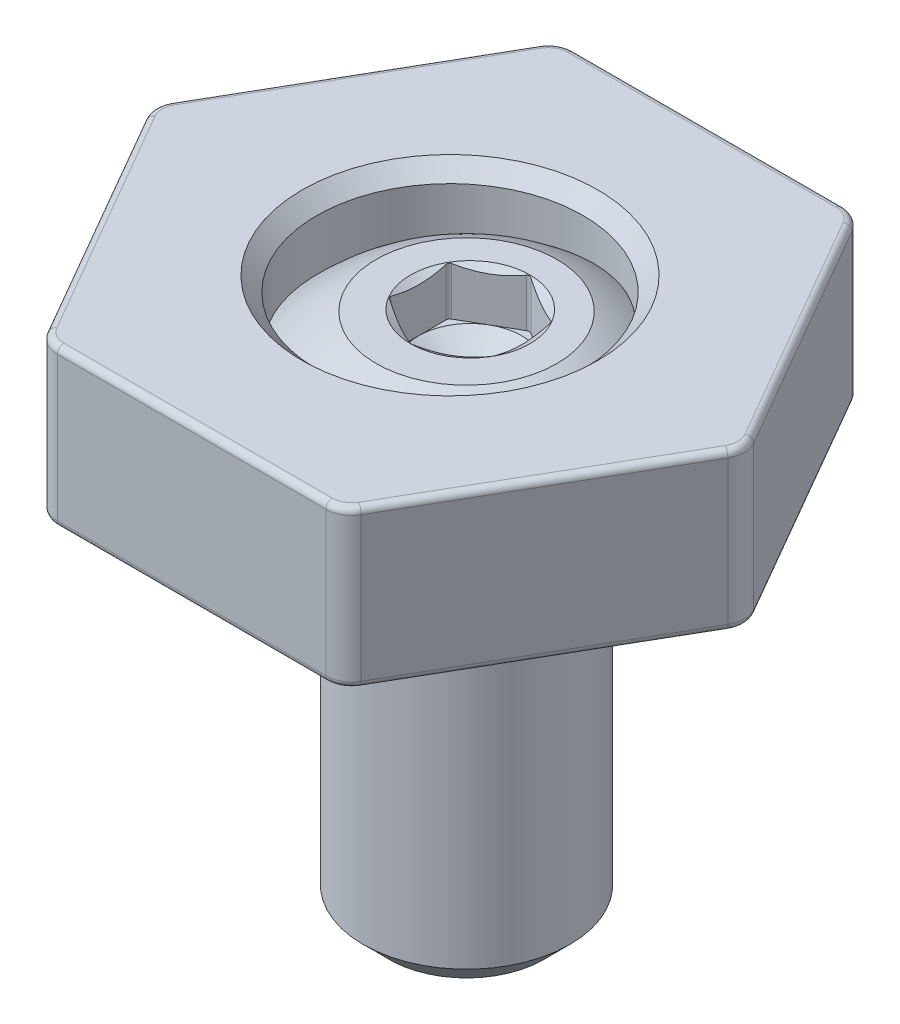
SolidWorks part; units mm, degrees
ref_plane "Front Plane" through (0, 0, 0) normal (0, 0, 1) x (1, 0, 0)
ref_plane "Top Plane" through (0, 0, 0) normal (0, 1, 0) x (1, 0, 0)
ref_plane "Right Plane" through (0, 0, 0) normal (1, 0, 0) x (0, 0, -1)
sketch "Sketch1" plane through (0, 0, 0) normal (0, 0, 1) x (1, 0, 0)
  line L0 (0, -8.382) -> (0, 8.382) construction
  line L1 (-4.0894, 8.382) -> (-7.9375, 8.382) construction
  line L2 (-7.9375, 8.382) -> (-7.9375, 3.556) construction
  line L9 (-4.0894, 8.382) -> (-4.0894, 4.318) construction
  line L10 (-3.8735, 3.556) -> (-7.9375, 3.556) construction
  line L11 (-4.0894, 4.318) -> (-3.8735, 4.318) construction
  line L12 (-3.8735, 4.318) -> (-3.8735, 3.556) construction
  line L13 (0.508, -8.382) -> (0.508, 8.382) construction
  line L14 (0.508, -8.382) -> (3.683, -8.382) construction
  line L15 (3.683, -8.382) -> (3.683, 4.318) construction
  line L16 (3.683, -8.382) -> (4.953, -8.382) construction
  line L17 (3.683, 4.318) -> (4.0259, 4.318) construction
  line L18 (4.0259, 4.318) -> (4.0259, 7.6708) construction
  arc A0 (4.0259, 7.2515) -> (3.283, 7.6708) centre (0.508, 1.8857) ccw construction
  point P3 (0, 0)
  point P26 (0.508, 6.1722)
  dimension "Screw Head Radius" = 6.4162
  dimension "Head C'Bore" = 8.1788
  dimension "Head Height" = 4.826
  dimension "Head ID" = 7.747
  dimension "Thread Length" = 11.938
  dimension "Maximum Head Movement" = 1.016
  dimension "Thread Size" = 6.35
  dimension "Pitch" = 1.27
  dimension "Shank Length" = 12.7
  dimension "Screw Head Diameter" = 8.0518
  dimension "Screw Head Height" = 3.3528
  dimension "Head Radius Center Offset" = 10.2677
  dimension "Drive Depth" = 2.2098
  dimension "Head Width" = 15.875
sketch "Sketch2" plane through (0, 0, 0) normal (0, 1, 0) x (1, 0, 0)
  line L0 (0.508, -1.7188) -> (0.508, 1.9474) construction
  line L1 (-1.0795, 1.0308) -> (-1.0795, -0.8022) construction
  line L2 (-1.0795, -0.8022) -> (0.508, -1.7188) construction
  line L3 (0.508, -1.7188) -> (2.0955, -0.8022) construction
  line L4 (2.0955, -0.8022) -> (2.0955, 1.0308) construction
  line L5 (2.0955, 1.0308) -> (0.508, 1.9474) construction
  line L6 (0.508, 1.9474) -> (-1.0795, 1.0308) construction
  line L7 (-3.8735, 0) -> (-7.9375, 0) construction
  line L8 (9.1654, 0) -> (4.5827, 7.9375)
  line L9 (4.5827, 7.9375) -> (-4.5827, 7.9375)
  line L10 (-4.5827, 7.9375) -> (-9.1654, 0)
  line L11 (-9.1654, 0) -> (-4.5827, -7.9375)
  line L12 (-4.5827, -7.9375) -> (4.5827, -7.9375)
  line L13 (4.5827, -7.9375) -> (9.1654, 0)
  circle A0 centre (0.508, 0.1143) radius 1.5875 construction
  circle A1 centre (0, 0) radius 7.9375 construction
  point P1 (0, 0)
  point P12 (1.016, 0)
  point P26 (-7.9375, 0)
  point P29 (0.508, 0)
  dimension "Drive Size" = 3.175
  dimension "Drill Location" = 7.8232
sketch "Sketch3" plane through (0, 0, 0) normal (0, 0, 1) x (1, 0, 0)
  line L0 (-3.8735, 3.556) -> (-7.9375, 3.556) construction
  line L1 (-4.543, 8.382) -> (-4.0894, 7.9284)
  line L8 (-4.0894, 8.382) -> (-7.9375, 8.382) construction
  line L9 (-4.0894, 8.382) -> (-4.0894, 4.318) construction
  line L10 (-4.0894, 4.318) -> (-3.8735, 4.318) construction
  line L11 (-3.8735, 4.318) -> (-3.8735, 3.556) construction
  line L12 (-3.8735, 3.556) -> (-7.9375, 3.556)
  line L20 (-4.543, 8.382) -> (-7.9375, 8.382)
  line L21 (-4.0894, 7.9284) -> (-4.0894, 4.318)
  line L22 (-4.0894, 4.318) -> (-3.8735, 4.318)
  line L23 (-3.8735, 4.318) -> (-3.8735, 3.556)
  line L24 (0, -8.382) -> (0, 8.382) construction
  line L25 (0, -8.382) -> (0, 8.382) construction
  line L26 (-7.9375, 8.382) -> (-7.9375, 3.556)
  dimension "D1" = 45
  dimension "D2" = 0.4536
revolve "Revolve1" add sketch "Sketch3" angle 360 about L25
sketch "Sketch4" plane through (0, 8.382, 0) normal (0, 1, 0) x (1, 0, 0)
  line L1 (4.1244, 7.9375) -> (-4.1244, 7.9375)
  line L2 (-4.8119, 7.5406) -> (-8.9363, 0.3969)
  line L3 (-8.9363, -0.3969) -> (-4.8119, -7.5406)
  line L4 (-4.1244, -7.9375) -> (4.1244, -7.9375)
  line L5 (4.8119, -7.5406) -> (8.9363, -0.3969)
  line L6 (8.9363, 0.3969) -> (4.8119, 7.5406)
  circle A0 centre (0, 0) radius 7.9375 construction
  circle A1 centre (0, 0) radius 7.9375 construction
  arc A2 (4.1244, 7.9375) -> (4.8119, 7.5406) centre (4.1244, 7.1438) cw
  arc A3 (-4.1244, 7.9375) -> (-4.8119, 7.5406) centre (-4.1244, 7.1437) ccw
  arc A4 (-8.9363, 0.3969) -> (-8.9363, -0.3969) centre (-8.2489, 0) ccw
  arc A5 (-4.8119, -7.5406) -> (-4.1244, -7.9375) centre (-4.1244, -7.1438) ccw
  arc A6 (4.1244, -7.9375) -> (4.8119, -7.5406) centre (4.1244, -7.1438) ccw
  arc A7 (8.9363, -0.3969) -> (8.9363, 0.3969) centre (8.2489, 0) ccw
  circle A9 centre (0, 0) radius 4.543
  circle A10 centre (0, 0) radius 4.543 construction
  dimension "D1" = 0.7937
extrude "Boss-Extrude1" add sketch "Sketch4" against normal up to surface (4.826 mm away) up to face at (3.8735, 3.556, 0)
fillet "Fillet1" radius 0.1984 24 edges at (-4.5213, 8.382, -7.8312) (0, 8.382, -7.9375) (4.5213, 8.382, -7.8312) (6.8741, 8.382, -3.9688) (9.0426, 8.382, 0) (6.8741, 8.382, 3.9688) (4.5213, 8.382, 7.8312) (0, 8.382, 7.9375) (-4.5213, 8.382, 7.8312) (-6.8741, 8.382, 3.9688) (-9.0426, 8.382, 0) (-9.0426, 3.556, 0) (-6.8741, 3.556, 3.9688) (-4.5213, 3.556, 7.8312) (0, 3.556, 7.9375) (4.5213, 3.556, 7.8312) (6.8741, 3.556, 3.9688) (9.0426, 3.556, 0) (6.8741, 3.556, -3.9688) (4.5213, 3.556, -7.8312) (0, 3.556, -7.9375) (-4.5213, 3.556, -7.8312) (-6.8741, 8.382, -3.9688) (-6.8741, 3.556, -3.9688)
sketch "Sketch5" plane through (0, 0, 0) normal (0, 0, 1) x (1, 0, 0)
  line L0 (0, -8.382) -> (0, 8.382) construction
  line L1 (0, -8.382) -> (0, 8.382) construction
  line L2 (0, 4.318) -> (4.0259, 4.318)
  line L3 (4.0259, 4.318) -> (4.0259, 7.6708)
  line L4 (4.0259, 7.6708) -> (0, 7.6708)
  line L5 (0, 7.6708) -> (0, 4.318) construction
  line L6 (0, 4.318) -> (0, 7.6708)
revolve "Revolve2" add sketch "Sketch5" angle 360 about L6
sketch "Sketch6" plane through (0, 0, 0) normal (0, 0, 1) x (1, 0, 0)
  line L0 (0.508, -8.382) -> (0.508, 4.318) construction
  line L1 (0.508, -8.382) -> (0.508, 8.382) construction
  line L2 (-4.0259, 4.318) -> (4.0259, 4.318) construction
  line L3 (0.508, 4.318) -> (3.683, 4.318)
  line L4 (3.683, 4.318) -> (3.683, -7.5882)
  line L5 (3.683, -8.382) -> (3.683, 4.318) construction
  line L6 (3.683, -7.5882) -> (2.8893, -8.382)
  line L7 (0.508, -8.382) -> (3.683, -8.382) construction
  line L8 (2.8893, -8.382) -> (0.508, -8.382)
  line L9 (0.508, -8.382) -> (0.508, 4.318)
  point P12 (3.683, -2.667)
  dimension "D1" = 45
  dimension "D2" = 0.7937
  dimension "D3" = 5.715
revolve "Revolve3" add sketch "Sketch6" angle 360 about L0
sketch "Sketch7" plane through (0, 0, 0) normal (0, 0, 1) x (1, 0, 0)
  line L0 (0.508, -8.382) -> (0.508, 8.382) construction
  line L5 (6.703, 13.1279) -> (6.703, 3.556)
  line L6 (0.508, -8.382) -> (0.508, 8.3019) construction
  line L7 (0.508, 8.3019) -> (0.508, 13.1279)
  line L8 (0.508, 13.1279) -> (6.703, 13.1279)
  line L9 (-6.703, 8.382) -> (6.703, 8.382) construction
  line L10 (-7.9375, 8.382) -> (-7.9375, 3.556) construction
  line L11 (-3.8735, 3.556) -> (-7.9375, 3.556) construction
  arc A0 (6.703, 3.556) -> (0.508, 8.3019) centre (0.508, 1.8857) ccw
  arc A1 (4.0259, 7.2515) -> (3.283, 7.6708) centre (0.508, 1.8857) ccw construction
  point P14 (0, 8.382)
revolve "Cut-Revolve1" cut sketch "Sketch7" angle 360 about L0
sketch "Sketch8" plane through (0, 7.6708, 0) normal (0, 1, 0) x (1, 0, 0)
  line L0 (-1.0795, -0.8022) -> (0.508, -1.7188) construction
  line L1 (0.508, -1.7188) -> (2.0955, -0.8022) construction
  line L2 (2.0955, -0.8022) -> (2.0955, 1.0308) construction
  line L3 (2.0955, 1.0308) -> (0.508, 1.9474) construction
  line L4 (0.508, 1.9474) -> (-1.0795, 1.0308) construction
  line L5 (-1.0795, 1.0308) -> (-1.0795, -0.8022) construction
  line L6 (-1.016, -0.8389) -> (0.4445, -1.6821)
  line L7 (0.5715, -1.6821) -> (2.032, -0.8389)
  line L8 (2.0955, -0.7289) -> (2.0955, 0.9575)
  line L9 (2.032, 1.0675) -> (0.5715, 1.9107)
  line L10 (0.4445, 1.9107) -> (-1.016, 1.0675)
  line L11 (-1.0795, 0.9575) -> (-1.0795, -0.7289)
  arc A0 (0.5715, 1.9107) -> (0.4445, 1.9107) centre (0.508, 1.8007) ccw
  arc A1 (2.0955, 0.9575) -> (2.032, 1.0675) centre (1.9685, 0.9575) ccw
  arc A2 (2.032, -0.8389) -> (2.0955, -0.7289) centre (1.9685, -0.7289) ccw
  arc A3 (-1.016, 1.0675) -> (-1.0795, 0.9575) centre (-0.9525, 0.9575) ccw
  arc A4 (0.4445, -1.6821) -> (0.5715, -1.6821) centre (0.508, -1.5721) ccw
  arc A5 (-1.016, -0.8389) -> (-1.0795, -0.7289) centre (-0.9525, -0.7289) cw
  dimension "D1" = 0.127
extrude "Cut-Extrude1" cut sketch "Sketch8" against normal up to vertex (1.4986 mm away) up to point (0.508, 6.1722, 0)
sketch "Sketch9" plane through (0, 6.1722, 0) normal (0, 1, 0) x (1, 0, 0)
  circle A0 centre (0.508, 0.1143) radius 1.5875 construction
  circle A1 centre (0.508, 0.1143) radius 1.5875
extrude "Cut-Extrude2" cut sketch "Sketch9" against normal through all draft 59
sketch "Sketch10" plane through (0, 7.6708, 0) normal (0, 1, 0) x (1, 0, 0)
  circle A0 centre (0.508, 0.1143) radius 1.8331
extrude "Cut-Extrude3" cut sketch "Sketch10" against normal through all draft 60
sketch "Sketch11" [suppressed] plane through (0, -8.382, 0) normal (0, -1, 0) x (1, 0, 0)
  circle A0 centre (0.508, 0) radius 3.175 construction
  circle A1 centre (0.508, 0) radius 3.175
curve "Helix/Spiral1" [suppressed] pitch 1.27 height 12.7 turns 10
sketch "Sketch12" [suppressed] plane through (0, 0, 0) normal (0, 0, 1) x (1, 0, 0)
  line L0 (-2.8045, -9.5726) -> (-1.7046, -8.9376) construction
  line L1 (-1.7046, -8.9376) -> (-2.8045, -8.3026) construction
  line L2 (-2.8045, -8.3026) -> (-2.8045, -9.5726) construction
  line L3 (-2.667, -9.4932) -> (-2.667, -8.382) construction
  line L4 (-2.8045, -8.9376) -> (-2.667, -8.9376) construction
  line L5 (-2.667, -8.9376) -> (-1.8421, -8.9376) construction
  line L6 (-1.8421, -8.9376) -> (-1.7046, -8.9376) construction
  line L7 (-1.8421, -9.017) -> (-1.8421, -8.8582)
  line L8 (-2.7357, -9.5329) -> (-2.7357, -8.3423)
  line L9 (-1.8421, -8.8582) -> (-2.7357, -8.3423)
  line L10 (-1.8421, -9.017) -> (-2.7357, -9.5329)
  line L11 (-2.667, 4.318) -> (-2.667, -7.5882) construction
  line L12 (-1.8732, -8.382) -> (2.8893, -8.382) construction
  point P12 (-2.7357, -8.9376)
  dimension "D1" = 1.27
  dimension "D2" = 0.1588
sweep "Cut-Sweep1" [suppressed] cut profiles "Sketch12" path "Helix/Spiral1"
equation "\"D2@Sketch6\" = \"Thread Size@Sketch1\" / 8"
equation "\"D3@Helix/Spiral1\"=\"Shank Length@Sketch1\""
equation "\"D4@Helix/Spiral1\"=\"Pitch@Sketch1\""
equation "\"D2@Sketch12\" = \"D1@Sketch12\" / 8"
equation "\"D1@Sketch12\" = \"Pitch@Sketch1\""
equation "\"D3@Sketch6\" = \"Pitch@Sketch1\" * 4.5"
equation "\"D1@Sketch4\" = \"Head Width@Sketch1\" / 20"
equation "\"D1@Sketch8\"=\"Drive Size@Sketch2\"/25"
equation "\"D2@Sketch3\"=\"Head Width@Sketch1\"/35"
